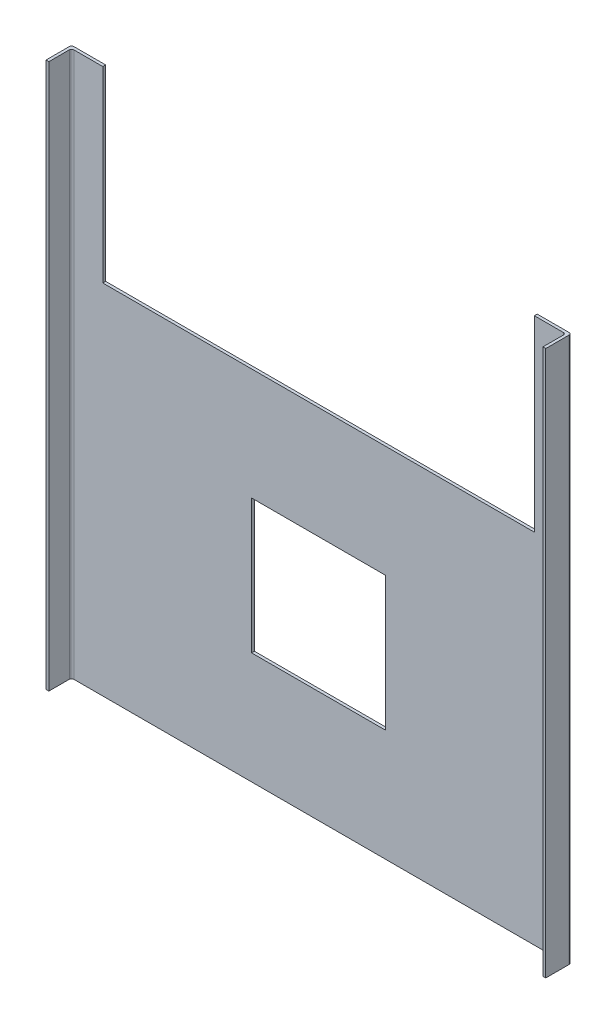
SolidWorks part; units mm, degrees
ref_plane "Front Plane" through (0, 0, 0) normal (0, 0, 1) x (1, 0, 0)
ref_plane "Top Plane" through (0, 0, 0) normal (0, 1, 0) x (1, 0, 0)
ref_plane "Right Plane" through (0, 0, 0) normal (1, 0, 0) x (0, 0, -1)
sketch "Sketch1" plane through (0, 0, 0) normal (0, 0, 1) x (1, 0, 0)
  line L0 (1041.4, 1219.2) -> (1117.6, 1219.2)
  line L1 (0, 0) -> (1117.6, 0)
  line L2 (0, 0) -> (0, 1219.2)
  line L3 (0, 1219.2) -> (76.2, 1219.2)
  line L4 (1117.6, 0) -> (1117.6, 1219.2)
  line L6 (76.2, 1219.2) -> (76.2, 800)
  line L7 (76.2, 800) -> (1041.4, 800)
  line L8 (1041.4, 1219.2) -> (1041.4, 800)
  dimension "D1" = 1117.6
  dimension "D2" = 1219.2
  dimension "D3" = 76.2
  dimension "D4" = 76.2
  dimension "D5" = 419.2
extrude "Boss-Extrude1" add sketch "Sketch1" along normal blind 6.35 contours L3 L6 L7 L8 L0 L4 L1 L2
sketch "Sketch2" plane through (0, 0, 6.35) normal (0, 0, 1) x (1, 0, 0)
  line L0 (0, 0) -> (1117.6, 0) construction
  line L1 (0, 1219.2) -> (6.35, 1219.2)
  line L2 (0, 1219.2) -> (0, 0)
  line L3 (0, 0) -> (6.35, 0)
  line L4 (6.35, 1219.2) -> (6.35, 0)
  line L6 (1117.6, 1219.2) -> (1111.25, 1219.2)
  line L7 (1117.6, 1219.2) -> (1117.6, 0)
  line L8 (1117.6, 0) -> (1111.25, 0)
  line L9 (1111.25, 1219.2) -> (1111.25, 0)
  dimension "D1" = 6.35
extrude "Boss-Extrude2" add sketch "Sketch2" along normal blind 50.8
fillet "Fillet1" radius 5 4 edges at (1117.6, 609.6, 0) (0, 609.6, 0) (1111.25, 609.6, 6.35) (6.35, 609.6, 6.35)
sketch "Sketch3" plane through (0, 0, 0) normal (0, 0, -1) x (-1, 0, 0)
  line L0 (-558.8, 800) -> (-558.8, 0) construction
  line L1 (-76.2, 800) -> (-1041.4, 800) construction
  line L2 (-5, 0) -> (-1112.6, 0) construction
  line L4 (-708.8, 250) -> (-408.8, 250)
  line L5 (-708.8, 250) -> (-708.8, 550)
  line L6 (-708.8, 550) -> (-408.8, 550)
  line L7 (-408.8, 250) -> (-408.8, 550)
  line L8 (-708.8, 250) -> (-408.8, 550) construction
  line L9 (-708.8, 550) -> (-408.8, 250) construction
  point P6 (-558.8, 400)
  dimension "D1" = 300
  dimension "D2" = 300
extrude "Cut-Extrude1" cut sketch "Sketch3" against normal through all
